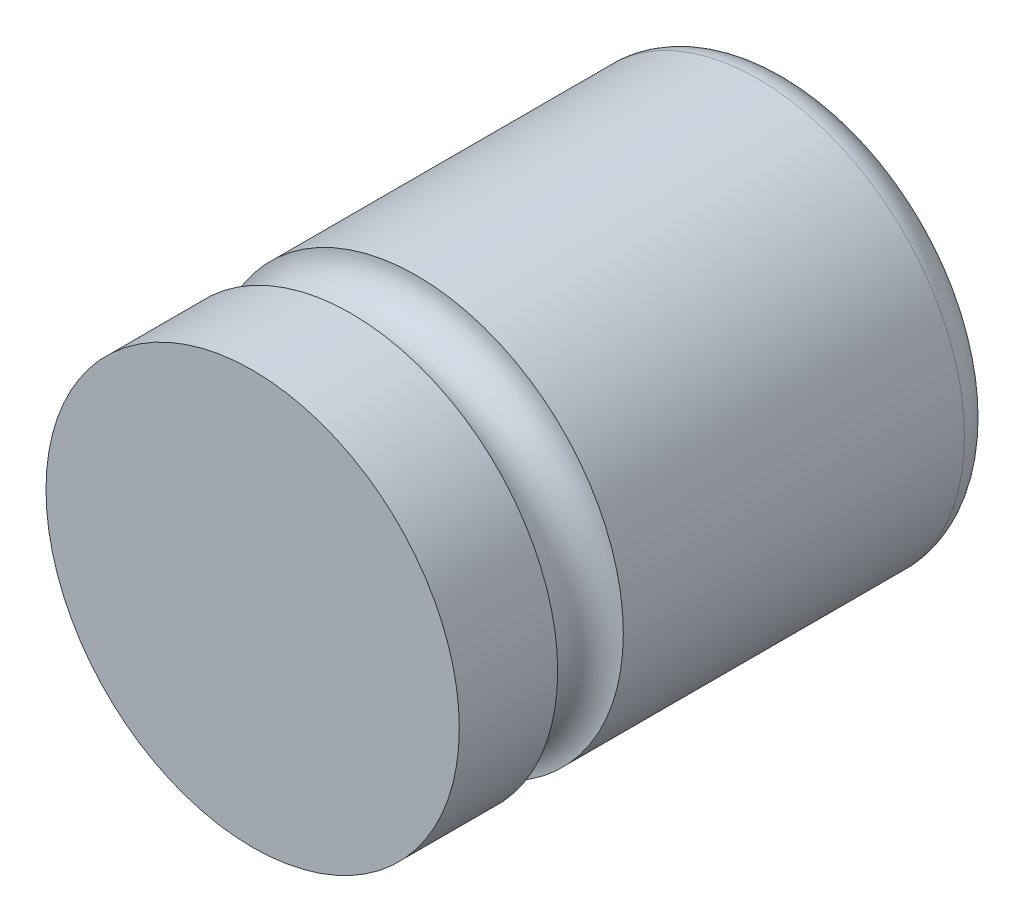
SolidWorks part; units mm, degrees
ref_plane "Front Plane" through (0, 0, 0) normal (0, 0, 1) x (1, 0, 0)
ref_plane "Top Plane" through (0, 0, 0) normal (0, 1, 0) x (1, 0, 0)
ref_plane "Right Plane" through (0, 0, 0) normal (1, 0, 0) x (0, 0, -1)
ref_axis "Axis1" through (0, 0, 0.41) along (0, 0, -1)
sketch "Sketch1" plane through (0, 0, 0) normal (0, 1, 0) x (1, 0, 0)
  line L0 (-55, 0) -> (55, 0) construction
  line L1 (0, 0) -> (3.15, 0)
  line L2 (0, 0) -> (0, 8.2)
  line L3 (0, 8.2) -> (2.65, 8.2)
  line L4 (3.15, 0) -> (3.15, 1.5)
  line L5 (3.15, 2.5) -> (3.15, 7.7)
  arc A0 (3.15, 2.5) -> (3.15, 1.5) centre (3.15, 2) ccw
  arc A1 (2.65, 8.2) -> (3.15, 7.7) centre (2.65, 7.7) cw
  point P7 (0, 0)
  point P12 (3.15, 8.2)
  dimension "D3" = 1
  dimension "D5" = 0.5
  dimension "D1" = 8.2
  dimension "D2" = 3.15
  dimension "D4" = 2
revolve "Revolve1" add sketch "Sketch1" angle 360 about L2
sketch "Sketch2" plane through (0, 0, -8.2) normal (0, 0, -1) x (-1, 0, 0)
  line L0 (1.5, 2.1846) -> (1.5, -2.1846)
  line L1 (0, 3.465) -> (0, -3.465) construction
  circle A0 centre (0, 0) radius 2.65 construction
  arc A1 (1.5, -2.1846) -> (1.5, 2.1846) centre (0, 0) ccw
  point P7 (0, 0)
  point P8 (0, 0)
  dimension "D1" = 1.5
extrude "Cut-Extrude1" cut sketch "Sketch2" against normal blind 0.01
